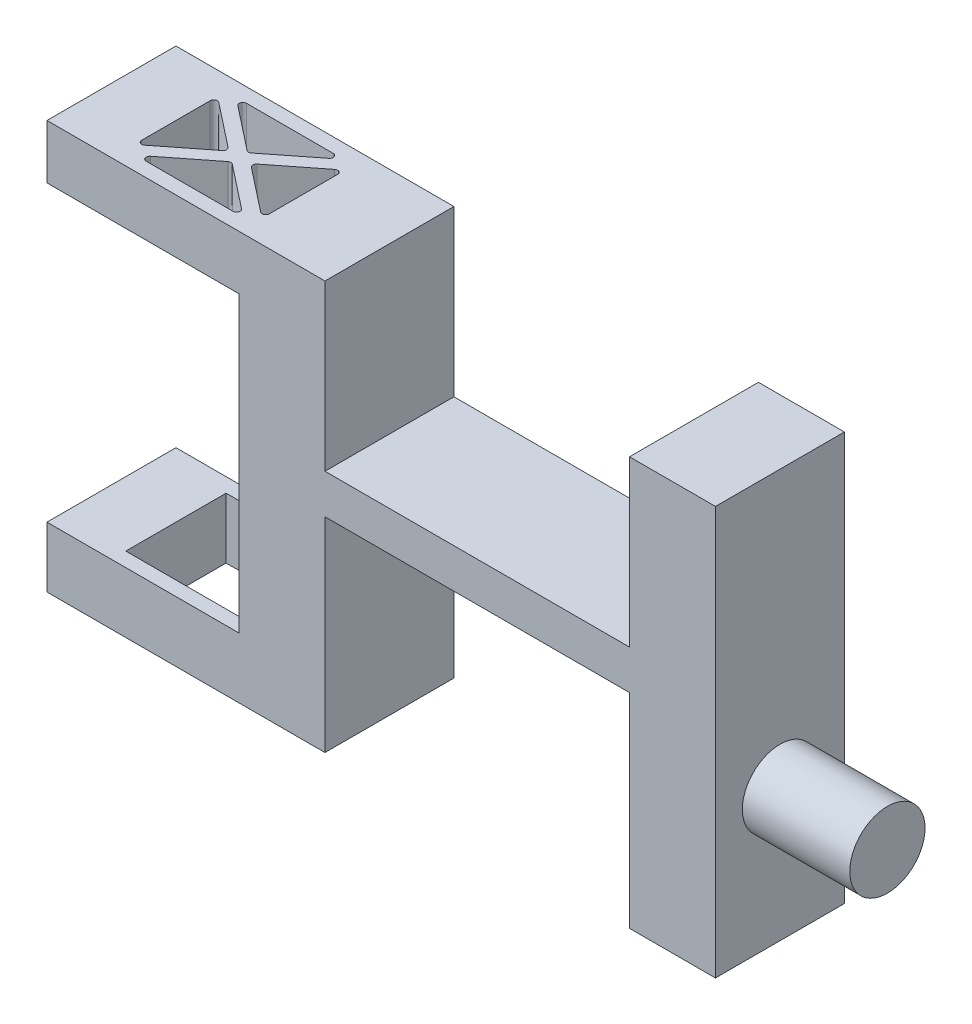
SolidWorks part; units mm, degrees
material "PLA"
ref_plane "Front Plane" through (0, 0, 0) normal (0, 0, 1) x (1, 0, 0)
ref_plane "Top Plane" through (0, 0, 0) normal (0, 1, 0) x (1, 0, 0)
ref_plane "Right Plane" through (0, 0, 0) normal (1, 0, 0) x (0, 0, -1)
sketch "Sketch2" plane through (0, 0, 0) normal (0, 0, 1) x (1, 0, 0)
  line L0 (0, -55) -> (0, 55) construction
  line L1 (0, 55) -> (66.5, 55)
  line L2 (0, 55) -> (0, 0)
  line L3 (0, 0) -> (66.5, 0)
  line L4 (66.5, 55) -> (66.5, 0)
  line L5 (55, 0) -> (-55, 0) construction
  line L7 (12, 50.75) -> (54.5, 50.75)
  line L8 (12, 50.75) -> (12, 30.25)
  line L9 (12, 30.25) -> (54.5, 30.25)
  line L10 (54.5, 50.75) -> (54.5, 30.25)
  line L11 (12, 24.75) -> (54.5, 24.75)
  line L12 (12, 24.75) -> (12, 4.25)
  line L13 (12, 4.25) -> (54.5, 4.25)
  line L14 (54.5, 24.75) -> (54.5, 4.25)
  dimension "D1" = 55
  dimension "D2" = 12
  dimension "D3" = 42.5
  dimension "D4" = 20.5
  dimension "D5" = 5.5
  dimension "D6" = 42.5
  dimension "D7" = 20.5
  dimension "D8" = 12
  dimension "D9" = 4.25
  dimension "D10" = 12
extrude "Boss-Extrude1" add sketch "Sketch2" along normal blind 18
sketch "Sketch3" plane through (0, 0, 18) normal (0, 0, 1) x (1, 0, 0)
  line L2 (12, 24.75) -> (12, 4.25) construction
  line L3 (54.5, 24.75) -> (12, 24.75) construction
  circle A8 centre (8.15, 19.75) radius 2.5
  circle A9 centre (8.15, 9.75) radius 2.5
  circle A10 centre (57.85, 9.75) radius 2.5
  circle A11 centre (57.85, 19.75) radius 2.5
  dimension "D9" = 45.85
  dimension "D10" = 45.85
  dimension "D11" = 5
  dimension "D12" = 5
  dimension "D13" = 3.85
  dimension "D14" = 3.85
  dimension "D15" = 10
  dimension "D16" = 5
  dimension "D17" = 5
  dimension "D18" = 5
  dimension "D19" = 5
  dimension "D24" = 10
sketch "Sketch5" plane through (0, 0, 0) normal (-1, 0, 0) x (0, 0, 1)
  line L0 (0, -55) -> (0, 55) construction
  line L1 (0, 55) -> (2, 55)
  line L2 (0, 55) -> (0, 49)
  line L3 (0, 49) -> (2, 49)
  line L4 (2, 55) -> (2, 49)
  line L5 (18, 55) -> (0, 55) construction
  line L6 (55, 0) -> (-55, 0) construction
  line L7 (18, 55) -> (16, 55)
  line L8 (18, 55) -> (18, 49)
  line L9 (18, 49) -> (16, 49)
  line L10 (16, 55) -> (16, 49)
  line L11 (0, 0) -> (2, 0)
  line L12 (0, 0) -> (0, 6)
  line L13 (0, 6) -> (2, 6)
  line L14 (2, 0) -> (2, 6)
  line L15 (18, 0) -> (16, 0)
  line L16 (18, 0) -> (18, 6)
  line L17 (18, 6) -> (16, 6)
  line L18 (16, 0) -> (16, 6)
  line L19 (18, 55) -> (18, 0) construction
  dimension "D1" = 2
  dimension "D2" = 2
  dimension "D3" = 6
  dimension "D4" = 6
  dimension "D5" = 2
  dimension "D6" = 2
  dimension "D7" = 6
  dimension "D8" = 6
extrude "Boss-Extrude2" add sketch "Sketch5" along normal blind 26.8
sketch "Sketch6" plane through (0, 0, 2) normal (0, 0, 1) x (1, 0, 0)
  line L0 (-26.8, 49) -> (0, 49) construction
  line L1 (-23.8, 49) -> (-26.8, 49)
  line L2 (-23.8, 49) -> (-23.8, 55)
  line L3 (-23.8, 55) -> (-26.8, 55)
  line L4 (-26.8, 49) -> (-26.8, 55)
  line L5 (66.5, 55) -> (-26.8, 55) construction
  line L6 (-26.8, 55) -> (-26.8, 49) construction
  line L7 (55, 0) -> (-55, 0) construction
  line L8 (-26.8, 6) -> (-24.8, 6)
  line L9 (-26.8, 6) -> (-26.8, 0)
  line L10 (-26.8, 0) -> (-24.8, 0)
  line L11 (-24.8, 6) -> (-24.8, 0)
  dimension "D1" = 3
  dimension "D2" = 2
extrude "Boss-Extrude3" add sketch "Sketch6" along normal up to next
sketch "Sketch8" plane through (0, 0, 18) normal (0, 0, 1) x (1, 0, 0)
  line L0 (66.5, 55) -> (-26.8, 55) construction
  line L1 (12, 50.75) -> (54, 50.75)
  line L2 (12, 50.75) -> (12, 55)
  line L3 (12, 55) -> (54, 55)
  line L4 (54, 50.75) -> (54, 55)
  line L5 (55, 0) -> (-55, 0) construction
  line L6 (12, 4.25) -> (54.5, 4.25)
  line L7 (12, 4.25) -> (12, 0)
  line L8 (12, 0) -> (54.5, 0)
  line L9 (54.5, 4.25) -> (54.5, 0)
extrude "Cut-Extrude3" cut sketch "Sketch8" against normal up to next
sketch "Sketch12" plane through (0, 0, 2) normal (0, 0, 1) x (1, 0, 0)
  line L0 (-26.8, 6) -> (0, 6) construction
  line L1 (-8, 6) -> (-5, 6)
  line L2 (-8, 6) -> (-8, 0)
  line L3 (-8, 0) -> (-5, 0)
  line L4 (-5, 6) -> (-5, 0)
  line L5 (55, 0) -> (-55, 0) construction
  line L6 (0, -55) -> (0, 55) construction
  dimension "D1" = 3
  dimension "D2" = 5
extrude "Boss-Extrude7" add sketch "Sketch12" along normal up to surface (14 mm away) up to face at (-12.4, 3, 16)
sketch "Sketch14" plane through (-8, 0, 0) normal (-1, 0, 0) x (0, 0, 1)
  line L0 (18, 6) -> (0, 6) construction
  line L1 (7, 6) -> (11, 6)
  line L2 (7, 6) -> (7, 0)
  line L3 (7, 0) -> (11, 0)
  line L4 (11, 6) -> (11, 0)
  line L5 (55, 0) -> (-55, 0) construction
  line L6 (0, -55) -> (0, 55) construction
  line L7 (18, 0) -> (18, 6) construction
  dimension "D1" = 7
  dimension "D2" = 7
extrude "Boss-Extrude8" add sketch "Sketch14" along normal up to surface (16.8 mm away) up to face at (-24.8, 3, 9)
sketch "Sketch17" plane through (0, 0, 2) normal (0, 0, 1) x (1, 0, 0)
  line L1 (-23.8, 55) -> (0, 55)
  line L2 (-23.8, 55) -> (-23.8, 49)
  line L3 (-23.8, 49) -> (0, 49)
  line L4 (0, 55) -> (0, 49)
extrude "Boss-Extrude9" add sketch "Sketch17" along normal blind 14 and the other way blind 1
sketch "Sketch18" plane through (0, 6, 0) normal (0, 1, 0) x (1, 0, 0)
  line L1 (-5, -2) -> (-24.8, -2)
  line L2 (-5, -2) -> (-5, -16)
  line L3 (-5, -16) -> (-24.8, -16)
  line L4 (-24.8, -2) -> (-24.8, -16)
extrude "Cut-Extrude4" cut sketch "Sketch18" against normal blind 10
sketch "Sketch20" plane through (0, 6, 0) normal (0, 1, 0) x (1, 0, 0)
  line L0 (-24.8, -16) -> (0, -16) construction
  line L1 (-24.8, -2) -> (-19.8, -2)
  line L2 (-24.8, -2) -> (-24.8, -16)
  line L3 (-24.8, -16) -> (-19.8, -16)
  line L4 (-19.8, -2) -> (-19.8, -16)
  dimension "D1" = 5
extrude "Boss-Extrude10" add sketch "Sketch20" against normal blind 6
sketch "Sketch22" plane through (0, 55, 0) normal (0, 1, 0) x (1, 0, 0)
  line L0 (-55, 0) -> (55, 0) construction
  line L1 (-26.8, -18) -> (12, -18)
  line L2 (-26.8, -18) -> (-26.8, 0)
  line L3 (-26.8, 0) -> (12, 0)
  line L4 (12, -18) -> (12, 0)
  line L5 (12, -18) -> (12, 0) construction
extrude "Boss-Extrude11" add sketch "Sketch22" along normal blind 1
sketch "Sketch23" plane through (0, 49, 0) normal (0, -1, 0) x (1, 0, 0)
  line L1 (0, 18) -> (-26.8, 18)
  line L2 (0, 18) -> (0, 0)
  line L3 (0, 0) -> (-26.8, 0)
  line L4 (-26.8, 18) -> (-26.8, 0)
extrude "Boss-Extrude12" add sketch "Sketch23" along normal blind 1
sketch "Sketch24" plane through (0, 6, 0) normal (0, 1, 0) x (1, 0, 0)
  line L0 (0, 0) -> (-26.8, 0)
  line L1 (-26.8, 0) -> (-26.8, -18)
  line L2 (-26.8, -18) -> (0, -18)
  line L3 (0, -18) -> (0, -16)
  line L4 (0, -16) -> (-19.8, -16)
  line L5 (-19.8, -16) -> (-19.8, -2)
  line L6 (-19.8, -2) -> (0, -2)
  line L7 (0, -2) -> (0, 0)
extrude "Boss-Extrude13" add sketch "Sketch24" along normal blind 1
sketch "Sketch25" plane through (0, 55, 0) normal (0, 1, 0) x (1, 0, 0)
  line L0 (-55, 0) -> (55, 0) construction
  line L1 (66.5, -18) -> (54.5, -18)
  line L2 (66.5, -18) -> (66.5, 0)
  line L3 (66.5, 0) -> (54.5, 0)
  line L4 (54.5, -18) -> (54.5, 0)
  line L5 (54.5, -18) -> (54.5, 0) construction
extrude "Boss-Extrude14" add sketch "Sketch25" along normal blind 1
sketch "Sketch27" plane through (0, 0, 0) normal (0, -1, 0) x (1, 0, 0)
  line L0 (-26.8, 18) -> (12, 18)
  line L1 (12, 18) -> (12, 0)
  line L2 (55, 0) -> (-55, 0) construction
  line L3 (12, 18) -> (12, 0) construction
  line L4 (12, 0) -> (-26.8, 0)
  line L5 (-26.8, 0) -> (-26.8, 18) construction
  line L6 (-26.8, 0) -> (-26.8, 18)
  line L7 (-19.8, 16) -> (-19.8, 2)
  line L8 (-19.8, 2) -> (0, 2)
  line L9 (0, 2) -> (0, 16)
  line L10 (0, 16) -> (0, 2) construction
  line L11 (-19.8, 16) -> (0, 16) construction
  line L12 (0, 16) -> (-19.8, 16)
extrude "Boss-Extrude15" add sketch "Sketch27" along normal blind 1
sketch "Sketch28" plane through (0, 0, 0) normal (0, -1, 0) x (1, 0, 0)
  line L0 (55, 0) -> (-55, 0) construction
  line L1 (54.5, 18) -> (66.5, 18)
  line L2 (54.5, 18) -> (54.5, 0)
  line L3 (54.5, 0) -> (66.5, 0)
  line L4 (66.5, 18) -> (66.5, 0)
  line L5 (66.5, 18) -> (66.5, 0) construction
extrude "Boss-Extrude16" add sketch "Sketch28" along normal blind 1
sketch "Sketch32" plane through (-26.8, 0, 0) normal (-1, 0, 0) x (0, 0, 1)
  line L0 (0, -55) -> (0, 55) construction
  line L1 (18, 7) -> (0, 7)
  line L2 (18, 7) -> (18, 4.25)
  line L3 (18, 4.25) -> (0, 4.25)
  line L4 (0, 7) -> (0, 4.25)
  dimension "D1" = 2.75
extrude "Cut-Extrude8" cut sketch "Sketch32" against normal blind 26.8
sketch "Sketch33" plane through (0, -1, 0) normal (0, -1, 0) x (1, 0, 0)
  line L0 (-26.8, 18) -> (12, 18)
  line L1 (12, 18) -> (12, 0)
  line L2 (31.35, 0) -> (-31.35, 0) construction
  line L3 (12, 18) -> (12, 0) construction
  line L4 (12, 0) -> (-26.8, 0)
  line L5 (-26.8, 18) -> (-26.8, 0) construction
  line L6 (-26.8, 0) -> (-26.8, 18)
  line L7 (-19.8, 16) -> (0, 16)
  line L8 (0, -9.9) -> (0, 9.9) construction
  line L9 (0, 16) -> (-19.8, 16) construction
  line L10 (0, 16) -> (0, 2)
  line L11 (0, 2) -> (-19.8, 2)
  line L12 (-19.8, 2) -> (-19.8, 16)
extrude "Boss-Extrude17" add sketch "Sketch33" along normal blind 2.75
sketch "Sketch34" plane through (0, -1, 0) normal (0, -1, 0) x (1, 0, 0)
  line L0 (31.35, 0) -> (-31.35, 0) construction
  line L1 (54.5, 18) -> (66.5, 18)
  line L2 (54.5, 18) -> (54.5, 0)
  line L3 (54.5, 0) -> (66.5, 0)
  line L4 (66.5, 18) -> (66.5, 0)
  line L5 (66.5, 0) -> (66.5, 18) construction
extrude "Boss-Extrude18" add sketch "Sketch34" along normal blind 2.75
sketch "Sketch35" plane through (0, 48, 0) normal (0, -1, 0) x (1, 0, 0)
  line L1 (-26.8, 18) -> (0, 18)
  line L2 (-26.8, 18) -> (-26.8, 0)
  line L3 (-26.8, 0) -> (0, 0)
  line L4 (0, 18) -> (0, 0)
extrude "Boss-Extrude19" add sketch "Sketch35" along normal blind 2.3
sketch "Sketch36" plane through (0, 56, 0) normal (0, 1, 0) x (1, 0, 0)
  line L0 (-31.35, 0) -> (31.35, 0) construction
  line L1 (66.5, -18) -> (54.5, -18)
  line L2 (66.5, -18) -> (66.5, 0)
  line L3 (66.5, 0) -> (54.5, 0)
  line L4 (54.5, -18) -> (54.5, 0)
  line L5 (54.5, -18) -> (54.5, 0) construction
  line L7 (12, -18) -> (-26.8, -18)
  line L8 (12, -18) -> (12, 0)
  line L9 (12, 0) -> (-26.8, 0)
  line L10 (-26.8, -18) -> (-26.8, 0)
extrude "Cut-Extrude9" cut sketch "Sketch36" against normal blind 2.75
sketch "Sketch37" plane through (-26.8, 0, 0) normal (-1, 0, 0) x (0, 0, 1)
  line L0 (0, 53.25) -> (18, 53.25) construction
  line L1 (0, -31.35) -> (0, 31.35) construction
  line L2 (18, 45.7) -> (18, 53.25) construction
  circle A0 centre (4, 49.45) radius 2.5
  circle A1 centre (14, 49.45) radius 2.5
  dimension "D1" = 3.8
  dimension "D2" = 4
  dimension "D3" = 4
  dimension "D4" = 3.8
  dimension "D5" = 5
  dimension "D6" = 5
sketch "Sketch38" plane through (-26.8, 0, 0) normal (-1, 0, 0) x (0, 0, 1)
  line L0 (0, 4.25) -> (18, 4.25) construction
  line L1 (0, -31.35) -> (0, 31.35) construction
  line L2 (18, -3.75) -> (18, 4.25) construction
  circle A0 centre (4, 0.45) radius 2.5
  circle A1 centre (14, 0.45) radius 2.5
  dimension "D1" = 3.8
  dimension "D2" = 5
  dimension "D3" = 4
  dimension "D4" = 5
  dimension "D5" = 4
  dimension "D6" = 3.8
extrude "Cut-Extrude10" cut sketch "Sketch37" against normal blind 6
sketch "Sketch39" plane through (0, 0, 0) normal (0, 0, -1) x (-1, 0, 0)
  line L0 (-54.5, 30.25) -> (-54.5, 27.5) construction
  line L2 (-54.5, 27.5) -> (-66.5, 27.5) construction
  line L3 (-66.5, -3.75) -> (-66.5, 53.25) construction
  circle A2 centre (-8.15, 19.75) radius 2.5
  circle A3 centre (-8.15, 9.75) radius 2.5
  circle A6 centre (-57.85, 19.75) radius 2.5
  circle A7 centre (-57.85, 9.75) radius 2.5
  circle A8 centre (-8.15, 45.25) radius 2.5
  circle A9 centre (-8.15, 35.25) radius 2.5
  circle A10 centre (-57.85, 45.25) radius 2.5
  circle A11 centre (-57.85, 35.25) radius 2.5
  dimension "D1" = 2.75
  dimension "D4" = 5
  dimension "D5" = 5
  dimension "D6" = 5
  dimension "D7" = 5
extrude "Cut-Extrude12" cut sketch "Sketch39" against normal blind 10
extrude "Cut-Extrude11" cut sketch "Sketch38" against normal blind 6
sketch "Sketch40" plane through (0, 0, 0) normal (0, 0, -1) x (-1, 0, 0)
  line L0 (-57.85, 35.25) -> (-8.15, 35.25) construction
  line L1 (-57.85, 19.75) -> (-8.15, 19.75) construction
  line L3 (-54, 50.75) -> (-54.5, 50.75)
  line L4 (-54, 50.75) -> (-54, 55)
  line L5 (-54, 55) -> (-54.5, 55)
  line L6 (-54.5, 50.75) -> (-54.5, 55)
extrude "Cut-Extrude13" cut sketch "Sketch40" against normal up to surface (18 mm away) up to face at (25.44, 30.97, 18)
sketch "Sketch43" plane through (0, 4.25, 0) normal (0, 1, 0) x (1, 0, 0)
  line L0 (0, 0) -> (-26.8, 0)
  line L1 (-26.8, 0) -> (-26.8, -18)
  line L2 (-26.8, -18) -> (0, -18)
  line L3 (0, -18) -> (0, -16)
  line L4 (0, -16) -> (-19.8, -16)
  line L5 (-19.8, -16) -> (-19.8, -2)
  line L6 (-19.8, -2) -> (0, -2)
  line L7 (0, -2) -> (0, 0)
extrude "Boss-Extrude21" add sketch "Sketch43" along normal blind 0.45
sketch "Sketch44" plane through (66.5, 0, 0) normal (1, 0, 0) x (0, 0, -1)
  line L0 (0, -3.75) -> (-18, -3.75) construction
  line L1 (-18, -3.75) -> (-18, 53.25) construction
  circle A0 centre (-9, 14.75) radius 5.25
  dimension "D1" = 10.5
  dimension "D2" = 18.5
  dimension "D3" = 9
extrude "Boss-Extrude22" add sketch "Sketch44" along normal blind 15
sketch "Sketch45" plane through (-19.8, 0, 0) normal (1, 0, 0) x (0, 0, -1)
  line L1 (-16, 4.7) -> (-2, 4.7)
  line L2 (-16, 4.7) -> (-16, -3.75)
  line L3 (-16, -3.75) -> (-2, -3.75)
  line L4 (-2, 4.7) -> (-2, -3.75)
  line L5 (-16, 4.7) -> (-2, -3.75) construction
  line L6 (-16, -3.75) -> (-2, 4.7) construction
  point P4 (-9, 0.475)
extrude "Boss-Extrude23" add sketch "Sketch45" along normal blind 2
sketch "Sketch48" plane through (0, 45.7, 0) normal (0, -1, 0) x (-1, 0, 0)
  line L0 (17.8, -16) -> (0, -2) construction
  line L1 (17.8, -16) -> (0, -16) construction
  line L2 (17.8, -16) -> (17.8, -2) construction
  line L3 (17.8, -2) -> (0, -2) construction
  line L4 (0, -16) -> (0, -2) construction
  line L5 (0, -16) -> (17.8, -2) construction
  line L6 (8.9, -16) -> (8.9, -2) construction
  line L7 (17.8, -9) -> (0, -9) construction
  line L8 (8.9, -16) -> (1.4, -16)
  line L9 (1.4, -16) -> (8.9, -10.1012)
  line L10 (8.9, -10.1012) -> (16.4, -16)
  line L11 (16.4, -16) -> (8.9, -16)
  line L12 (1.3986, -2) -> (8.9, -7.9)
  line L13 (8.9, -7.9) -> (16.4014, -2)
  line L14 (16.4014, -2) -> (1.3986, -2)
  line L15 (0, -9) -> (0, -3.2)
  line L16 (0, -3.2) -> (7.3743, -9)
  line L17 (7.3743, -9) -> (0, -14.8)
  line L18 (0, -14.8) -> (0, -3.2)
  line L19 (17.8, -3.1959) -> (10.4205, -9)
  line L20 (10.4205, -9) -> (17.8, -14.8041)
  line L21 (17.8, -14.8041) -> (17.8, -3.1959)
  point P15 (8.9, -9)
  dimension "D1" = 7.5
  dimension "D2" = 7.5
  dimension "D3" = 1.1
  dimension "D4" = 5.8
  dimension "D5" = 0.94
extrude "Cut-Extrude14" cut sketch "Sketch48" against normal through all contours L14 L12 L13 | L16 L17 L18 | L21 L19 L20 | L11 L8 L9 L10
fillet "Fillet1" radius 0.5 12 edges at (-1.3986, 49.475, 2) (-16.4014, 49.475, 2) (-17.8, 49.475, 3.1959) (-10.4205, 49.475, 9) (-17.8, 49.475, 14.8041) (-16.4, 49.475, 16) (-1.4, 49.475, 16) (-8.9, 49.475, 10.1012) (-7.3743, 49.475, 9) (0, 49.475, 3.2) (0, 49.475, 14.8) (-8.9, 49.475, 7.9)
